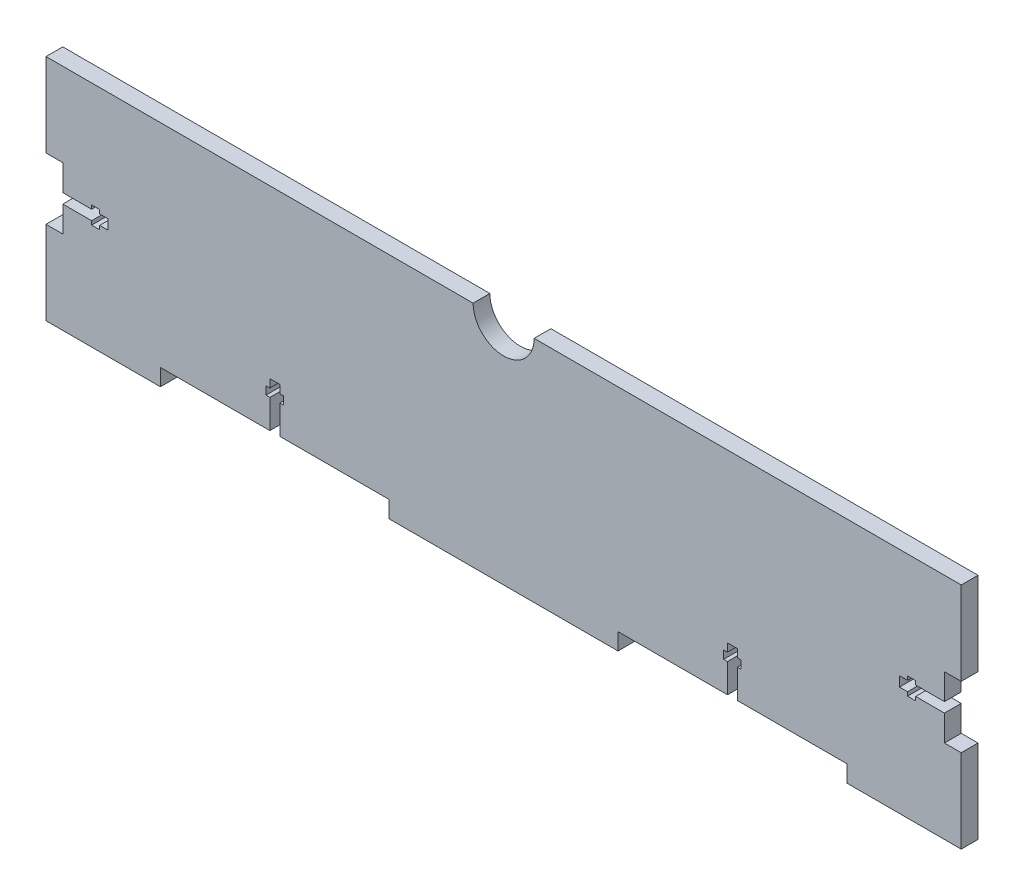
SolidWorks part; units mm, degrees
ref_plane "Front Plane" through (0, 0, 0) normal (0, 0, 1) x (1, 0, 0)
ref_plane "Top Plane" through (0, 0, 0) normal (0, 1, 0) x (1, 0, 0)
ref_plane "Right Plane" through (0, 0, 0) normal (1, 0, 0) x (0, 0, -1)
sketch "Sketch1" plane through (0, 0, 0) normal (0, 0, 1) x (1, 0, 0)
  line L0 (0, 78) -> (0, 50.625)
  line L1 (0, 50.625) -> (5.5, 50.625)
  line L2 (5.5, 50.625) -> (5.5, 42.125)
  line L3 (5.5, 42.125) -> (14.95, 42.125)
  line L4 (14.95, 42.125) -> (14.95, 43.375)
  line L5 (14.95, 43.375) -> (17.6, 43.375)
  line L6 (17.6, 43.375) -> (17.6, 42.125)
  line L7 (17.6, 42.125) -> (20.25, 42.125)
  line L8 (20.25, 42.125) -> (20.25, 38.875)
  line L9 (20.25, 38.875) -> (17.6, 38.875)
  line L10 (17.6, 38.875) -> (17.6, 37.625)
  line L11 (17.6, 37.625) -> (14.95, 37.625)
  line L12 (14.95, 37.625) -> (14.95, 38.875)
  line L13 (14.95, 38.875) -> (5.5, 38.875)
  line L14 (5.5, 38.875) -> (5.5, 30.375)
  line L15 (5.5, 30.375) -> (0, 30.375)
  line L16 (0, 30.375) -> (0, 3)
  line L17 (0, 3) -> (37.5, 3)
  line L18 (37.5, 3) -> (37.5, 8.5)
  line L19 (37.5, 8.5) -> (73.375, 8.5)
  line L20 (73.375, 8.5) -> (73.375, 17.95)
  line L21 (73.375, 17.95) -> (72.125, 17.95)
  line L22 (72.125, 17.95) -> (72.125, 20.6)
  line L23 (72.125, 20.6) -> (73.375, 20.6)
  line L24 (73.375, 20.6) -> (73.375, 23.25)
  line L25 (73.375, 23.25) -> (76.625, 23.25)
  line L26 (76.625, 23.25) -> (76.625, 20.6)
  line L27 (76.625, 20.6) -> (77.875, 20.6)
  line L28 (77.875, 20.6) -> (77.875, 17.95)
  line L29 (77.875, 17.95) -> (76.625, 17.95)
  line L30 (76.625, 17.95) -> (76.625, 8.5)
  line L31 (76.625, 8.5) -> (112.5, 8.5)
  line L32 (112.5, 8.5) -> (112.5, 3)
  line L33 (112.5, 3) -> (187.5, 3)
  line L34 (187.5, 3) -> (187.5, 8.5)
  line L35 (187.5, 8.5) -> (223.375, 8.5)
  line L36 (223.375, 8.5) -> (223.375, 17.95)
  line L37 (223.375, 17.95) -> (222.125, 17.95)
  line L38 (222.125, 17.95) -> (222.125, 20.6)
  line L39 (222.125, 20.6) -> (223.375, 20.6)
  line L40 (223.375, 20.6) -> (223.375, 23.25)
  line L41 (223.375, 23.25) -> (226.625, 23.25)
  line L42 (226.625, 23.25) -> (226.625, 20.6)
  line L43 (226.625, 20.6) -> (227.875, 20.6)
  line L44 (227.875, 20.6) -> (227.875, 17.95)
  line L45 (227.875, 17.95) -> (226.625, 17.95)
  line L46 (226.625, 17.95) -> (226.625, 8.5)
  line L47 (226.625, 8.5) -> (262.5, 8.5)
  line L48 (262.5, 8.5) -> (262.5, 3)
  line L49 (262.5, 3) -> (300, 3)
  line L50 (300, 3) -> (300, 30.375)
  line L51 (300, 30.375) -> (294.5, 30.375)
  line L52 (294.5, 30.375) -> (294.5, 38.875)
  line L53 (294.5, 38.875) -> (285.05, 38.875)
  line L54 (285.05, 38.875) -> (285.05, 37.625)
  line L55 (285.05, 37.625) -> (282.4, 37.625)
  line L56 (282.4, 37.625) -> (282.4, 38.875)
  line L57 (282.4, 38.875) -> (279.75, 38.875)
  line L58 (279.75, 38.875) -> (279.75, 42.125)
  line L59 (279.75, 42.125) -> (282.4, 42.125)
  line L60 (282.4, 42.125) -> (282.4, 43.375)
  line L61 (282.4, 43.375) -> (285.05, 43.375)
  line L62 (285.05, 43.375) -> (285.05, 42.125)
  line L63 (285.05, 42.125) -> (294.5, 42.125)
  line L64 (294.5, 42.125) -> (294.5, 50.625)
  line L65 (294.5, 50.625) -> (300, 50.625)
  line L66 (300, 50.625) -> (300, 78)
  line L67 (300, 78) -> (0, 78)
sketch "Sketch2" plane through (0, 0, 0) normal (0, 0, 1) x (1, 0, 0)
  line L0 (300, 78) -> (0, 78) construction
  circle A0 centre (150, 78) radius 10
  dimension "D1" = 20
extrude "Boss-Extrude1" add sketch "Sketch1" along normal blind 5.5
extrude "Cut-Extrude2" cut sketch "Sketch2" along normal through all
